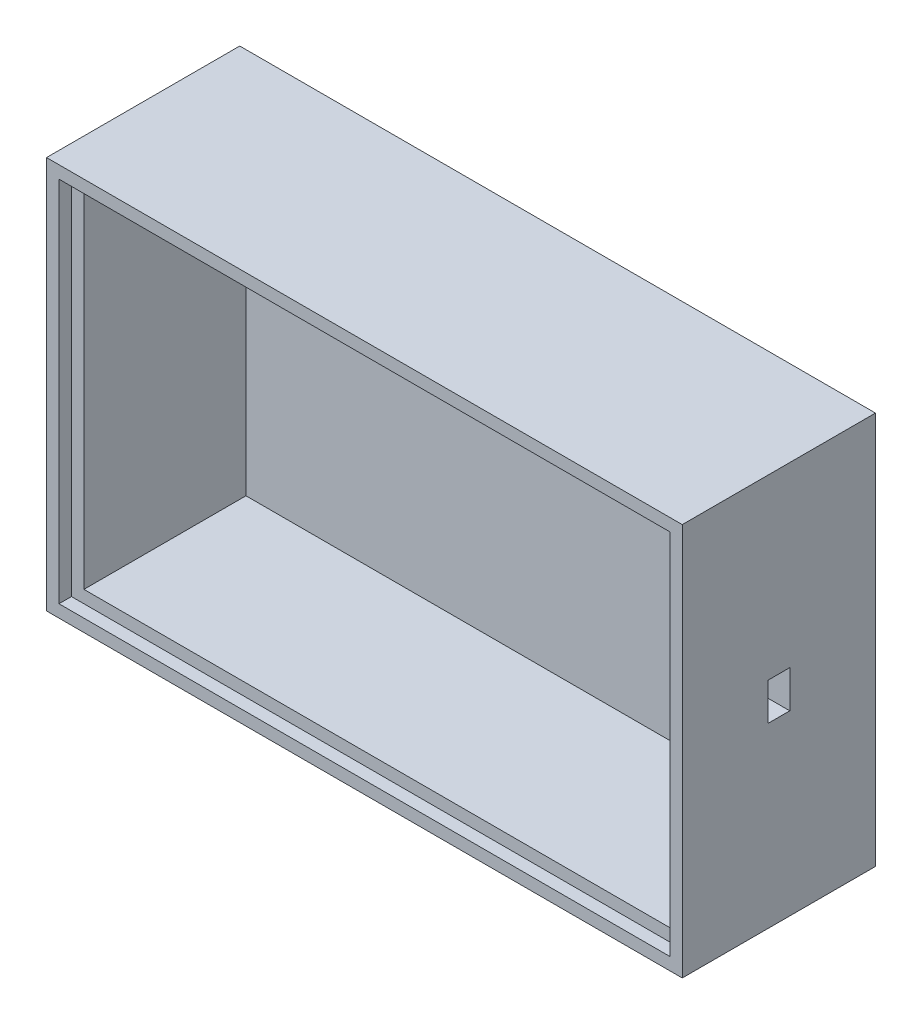
SolidWorks part; units mm, degrees
ref_plane "Přední rovina" through (0, 0, 0) normal (0, 0, 1) x (1, 0, 0)
ref_plane "Horní rovina" through (0, 0, 0) normal (0, 1, 0) x (1, 0, 0)
ref_plane "Pravá rovina" through (0, 0, 0) normal (1, 0, 0) x (0, 0, -1)
sketch "Skica1" plane through (0, 0, 0) normal (0, 0, 1) x (1, 0, 0)
  line L1 (0, 0) -> (98, 0)
  line L2 (0, 0) -> (0, 59)
  line L3 (0, 59) -> (98, 59)
  line L4 (98, 0) -> (98, 59)
  line L5 (-2, 61) -> (100, 61)
  line L6 (-2, 61) -> (-2, -2)
  line L7 (-2, -2) -> (100, -2)
  line L8 (100, 61) -> (100, -2)
  line L9 (2, 57) -> (96, 57)
  line L10 (2, 57) -> (2, 2)
  line L11 (2, 2) -> (96, 2)
  line L12 (96, 57) -> (96, 2)
  dimension "D1" = 102
  dimension "D2" = 63
  dimension "D3" = 2
  dimension "D4" = 2
  dimension "D5" = 2
  dimension "D6" = 2
  dimension "D7" = 2
  dimension "D8" = 2
  dimension "D9" = 2
  dimension "D10" = 2
  dimension "D11" = 55
  dimension "D12" = 94
extrude "Přidat vysunutím1" add sketch "Skica1" along normal blind 3 contours L6 L7 L8 L5
extrude "Přidat vysunutím2" add sketch "Skica1<4>" along normal blind 31 contours L8 L5 L6 L7 L4 L1 L2 L3 region at (49, 59.8011, 0)
sketch "Skica1<4>" plane through (0, 0, 0) normal (0, 0, 1) x (1, 0, 0) same geometry as "Skica1"
extrude "Přidat vysunutím3" add sketch "Skica1<5>" along normal blind 29 contours L1 L4 L3 L2 L9 L12 L11 L10 region at (1.1439, 29.5, 0)
sketch "Skica1<5>" plane through (0, 0, 0) normal (0, 0, 1) x (1, 0, 0) same geometry as "Skica1"
sketch "Skica2" plane through (100, 0, 0) normal (1, 0, 0) x (0, 0, -1)
  line L0 (-15.5, 61) -> (-15.5, -2) construction
  line L1 (-17.25, 26.5) -> (-13.75, 26.5)
  line L2 (-17.25, 26.5) -> (-17.25, 32.5)
  line L3 (-17.25, 32.5) -> (-13.75, 32.5)
  line L4 (-13.75, 26.5) -> (-13.75, 32.5)
  line L5 (-17.25, 26.5) -> (-13.75, 32.5) construction
  line L6 (-17.25, 32.5) -> (-13.75, 26.5) construction
  line L7 (-31, 61) -> (0, 61) construction
  line L8 (-31, -2) -> (0, -2) construction
  line L9 (-31, 29.5) -> (0, 29.5) construction
  line L10 (-31, 61) -> (-31, -2) construction
  line L11 (0, 61) -> (0, -2) construction
  point P0 (-15.5, 29.5)
  point P17 (-15.5, 29.5)
  dimension "D1" = 6
  dimension "D2" = 3.5
extrude "Odebrat vysunutím1" cut sketch "Skica2" against normal up to surface (4 mm away) up to face at (96, 29.5, 16)
